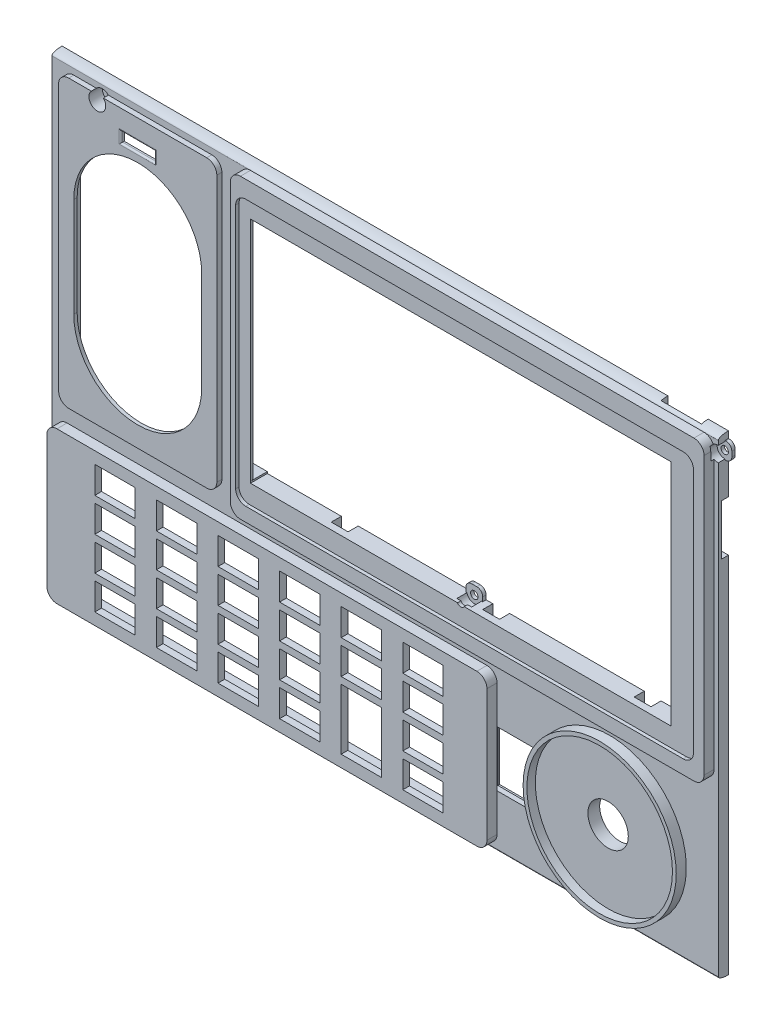
SolidWorks part; units mm, degrees
ref_plane "Front Plane" through (0, 0, 0) normal (0, 0, 1) x (1, 0, 0)
ref_plane "Top Plane" through (0, 0, 0) normal (0, 1, 0) x (1, 0, 0)
ref_plane "Right Plane" through (0, 0, 0) normal (1, 0, 0) x (0, 0, -1)
sketch "Sketch1" plane through (0, 0, 0) normal (0, 0, 1) x (1, 0, 0)
  line L1 (99, -70) -> (-99, -70)
  line L2 (99, -70) -> (99, 70)
  line L3 (99, 70) -> (-99, 70)
  line L4 (-99, -70) -> (-99, 70)
  line L5 (99, -70) -> (-99, 70) construction
  line L6 (99, 70) -> (-99, -70) construction
  point P0 (0, 0)
  dimension "D1" = 198
  dimension "D2" = 140
extrude "main_body" add sketch "Sketch1" along normal blind 3
fillet "long_corners" radius 3 2 edges at (0, 70, 3) (0, -70, 3) second distance 1 first distance on face at (0, 70, 1.5) first distance on face at (0, -70, 1.5)
sketch "Sketch2" plane through (0, 0, 3) normal (0, 0, 1) x (1, 0, 0)
  line L0 (-99, 24.75) -> (99, 24.75) construction
  line L1 (-99, 69) -> (-99, -69) construction
  line L2 (99, -69) -> (99, 69) construction
  line L3 (99, 69) -> (-99, 69) construction
  line L4 (-48.5, -17.75) -> (-95.5, -17.75)
  line L5 (-48.5, -17.75) -> (-48.5, 67.25)
  line L6 (-48.5, 67.25) -> (-95.5, 67.25)
  line L7 (-95.5, -17.75) -> (-95.5, 67.25)
  line L8 (-48.5, -17.75) -> (-95.5, 67.25) construction
  line L9 (-48.5, 67.25) -> (-95.5, -17.75) construction
  point P6 (-72, 24.75)
  dimension "D1" = 85
  dimension "D2" = 47
  dimension "D3" = 27
  dimension "D4" = 44.25
extrude "speaker" add sketch "Sketch2" along normal blind 1.5
fillet "speaker_corners" radius 3 4 edges at (-95.5, 67.25, 3.75) (-95.5, -17.75, 3.75) (-48.5, -17.75, 3.75) (-48.5, 67.25, 3.75)
sketch "Sketch19" plane through (0, 0, 4.5) normal (0, 0, 1) x (1, 0, 0)
  line L0 (-72, 67.25) -> (-72, -17.75) construction
  line L1 (-51.5, 67.25) -> (-92.5, 67.25) construction
  line L2 (-92.5, -17.75) -> (-51.5, -17.75) construction
  line L3 (-72, 7.25) -> (-72, 36.75) construction
  line L4 (-95.5, 64.25) -> (-95.5, -14.75) construction
  line L5 (-95.5, 24.75) -> (-48.5, 24.75) construction
  line L6 (-48.5, -14.75) -> (-48.5, 64.25) construction
  line L7 (-91, 7.25) -> (-91, 36.75)
  line L8 (-53, 7.25) -> (-53, 36.75)
  arc A0 (-91, 7.25) -> (-53, 7.25) centre (-72, 7.25) ccw
  arc A1 (-53, 36.75) -> (-91, 36.75) centre (-72, 36.75) ccw
  point P14 (-72, 22)
  point P19 (-72, -11.75)
  point P20 (-72, 55.75)
  dimension "D2" = 67.5
  dimension "D1" = 38
  dimension "D3" = 11.5
  dimension "D4" = 6
extrude "speaker_cut" cut sketch "Sketch19" against normal through all
sketch "Sketch21" plane through (0, 0, 0) normal (0, 0, -1) x (-1, 0, 0)
  line L0 (72, -11.75) -> (72, 55.75) construction
  line L2 (53, 7.25) -> (53, 36.75) construction
  line L3 (53, 22) -> (91, 22) construction
  line L4 (91, 36.75) -> (91, 7.25) construction
  line L5 (50.5, 61) -> (93.5, 61)
  line L6 (50.5, 61) -> (50.5, -17)
  line L7 (50.5, -17) -> (93.5, -17)
  line L8 (93.5, 61) -> (93.5, -17)
  line L9 (50.5, 61) -> (93.5, -17) construction
  line L10 (50.5, -17) -> (93.5, 61) construction
  arc A0 (53, 7.25) -> (91, 7.25) centre (72, 7.25) ccw construction
  arc A1 (91, 36.75) -> (53, 36.75) centre (72, 36.75) ccw construction
  point P14 (72, 22)
  dimension "D1" = 43
  dimension "D2" = 78
extrude "speaker_slot" cut sketch "Sketch21" against normal blind 3.5
sketch "Sketch3" plane through (0, 0, 3) normal (0, 0, 1) x (1, 0, 0)
  line L0 (-99, 24.875) -> (99, 24.875) construction
  line L1 (-99, 69) -> (-99, -69) construction
  line L2 (99, -69) -> (99, 69) construction
  line L4 (-48.5, -14.75) -> (-48.5, 64.25) construction
  line L5 (97.75, -19.25) -> (-43, -19.25)
  line L6 (97.75, -19.25) -> (97.75, 69)
  line L7 (97.75, 69) -> (-43, 69)
  line L8 (-43, -19.25) -> (-43, 69)
  line L9 (97.75, -19.25) -> (-43, 69) construction
  line L10 (97.75, 69) -> (-43, -19.25) construction
  line L11 (99, 70) -> (-99, 70) construction
  point P8 (27.375, 24.875)
  dimension "D1" = 1
  dimension "D2" = 88.25
  dimension "D3" = 140.75
  dimension "D4" = 1.25
  dimension "D5" = 5.5
extrude "lcd" add sketch "Sketch3" along normal blind 3
fillet "lcd_corners" radius 3 4 edges at (97.75, -19.25, 4.5) (-43, -19.25, 4.5)
sketch "Sketch9" plane through (0, 0, 6) normal (0, 0, 1) x (1, 0, 0)
  line L0 (-43, 24.375) -> (97.75, 24.375) construction
  line L1 (-43, 66) -> (-43, -16.25) construction
  line L2 (97.75, -16.25) -> (97.75, 66) construction
  line L3 (-40, -19.25) -> (94.75, -19.25) construction
  line L4 (94.6, -15.125) -> (-41.4, -15.125)
  line L5 (94.6, -15.125) -> (94.6, 63.875)
  line L6 (94.6, 63.875) -> (-41.4, 63.875)
  line L7 (-41.4, -15.125) -> (-41.4, 63.875)
  line L8 (94.6, -15.125) -> (-41.4, 63.875) construction
  line L9 (94.6, 63.875) -> (-41.4, -15.125) construction
  line L10 (94.75, 69) -> (-40, 69) construction
  line L11 (97.75, -16.25) -> (97.75, 66) construction
  point P6 (26.6, 24.375)
  dimension "D1" = 136
  dimension "D2" = 79
  dimension "D3" = 1.6
  dimension "D4" = 4.125
  dimension "D5" = 5.125
  dimension "D6" = 3.15
extrude "lcd_front" cut sketch "Sketch9" against normal blind 1
fillet "lcd_front_corners" radius 3 4 edges at (94.6, -15.125, 5.5) (94.6, 63.875, 5.5) (-41.4, 63.875, 5.5) (-41.4, -15.125, 5.5)
sketch "Sketch10" plane through (0, 0, 0) normal (0, 0, -1) x (-1, 0, 0)
  line L0 (-94.6, -12.125) -> (-94.6, 60.875) construction
  line L1 (-91.6, 63.875) -> (38.4, 63.875) construction
  line L2 (41.4, 63.875) -> (41.4, -15.125) construction
  line L3 (-94.6, 63.875) -> (41.4, 63.875) construction
  line L4 (38, -9.5) -> (-87, -9.5)
  line L5 (38, -9.5) -> (38, 58.5)
  line L6 (38, 58.5) -> (-87, 58.5)
  line L7 (-87, -9.5) -> (-87, 58.5)
  line L8 (-87, -9.5) -> (38, 58.5) construction
  line L9 (-87, 58.5) -> (38, -9.5) construction
  line L10 (-99, -70) -> (-99, 70) construction
  line L11 (-99, 70) -> (99, 70) construction
  line L13 (38.4, -15.125) -> (-91.6, -15.125) construction
  dimension "D1" = 125
  dimension "D2" = 68
  dimension "D3" = 12
  dimension "D4" = 3.4
  dimension "D5" = 11.5
  dimension "D6" = 5.375
  dimension "D7" = 7.6
  dimension "D8" = 5.375
  dimension "D9" = 5.625
extrude "lcd_back" cut sketch "Sketch10" against normal through all
sketch "Sketch56" plane through (0, 0, 0) normal (0, 0, -1) x (-1, 0, 0)
  line L0 (-87, -9.5) -> (38, -9.5) construction
  line L1 (-79, -9.5) -> (-74, -9.5)
  line L2 (-79, -9.5) -> (-79, -12.5)
  line L3 (-79, -12.5) -> (-74, -12.5)
  line L4 (-74, -9.5) -> (-74, -12.5)
  line L5 (38, 58.5) -> (-87, 58.5) construction
  line L6 (-34, -9.5) -> (-29, -9.5)
  line L7 (-34, -9.5) -> (-34, -12.5)
  line L8 (-34, -12.5) -> (-29, -12.5)
  line L9 (-29, -9.5) -> (-29, -12.5)
  line L10 (11, -9.5) -> (16, -9.5)
  line L11 (11, -9.5) -> (11, -12.5)
  line L12 (11, -12.5) -> (16, -12.5)
  line L13 (16, -9.5) -> (16, -12.5)
  line L14 (-79, 58.5) -> (-74, 58.5)
  line L15 (-79, 58.5) -> (-79, 61.5)
  line L16 (-79, 61.5) -> (-74, 61.5)
  line L17 (-74, 58.5) -> (-74, 61.5)
  line L18 (38, -9.5) -> (38, 58.5) construction
  line L19 (-34, 58.5) -> (-29, 58.5)
  line L20 (-34, 58.5) -> (-34, 61.5)
  line L21 (-34, 61.5) -> (-29, 61.5)
  line L22 (-29, 58.5) -> (-29, 61.5)
  line L23 (11, 58.5) -> (16, 58.5)
  line L24 (11, 58.5) -> (11, 61.5)
  line L25 (11, 61.5) -> (16, 61.5)
  line L26 (16, 58.5) -> (16, 61.5)
  line L27 (38, 58) -> (42, 58)
  line L28 (38, 58) -> (38, -9)
  line L29 (38, -9) -> (42, -9)
  line L30 (42, 58) -> (42, -9)
  line L31 (-99, -70) -> (-99, 70) construction
  line L32 (-99, 70) -> (99, 70) construction
  point P34 (-29, -11)
  dimension "D1" = 5
  dimension "D2" = 5
  dimension "D3" = 5
  dimension "D4" = 5
  dimension "D5" = 5
  dimension "D6" = 5
  dimension "D7" = 67
  dimension "D8" = 4
  dimension "D9" = 3
  dimension "D10" = 3
  dimension "D11" = 3
  dimension "D12" = 3
  dimension "D13" = 3
  dimension "D14" = 3
  dimension "D15" = 40
  dimension "D16" = 40
  dimension "D17" = 20
  dimension "D18" = 20
  dimension "D19" = 40
  dimension "D20" = 40
  dimension "D21" = 12
extrude "lcd_glue_points" cut sketch "Sketch56" against normal blind 3
sketch "Sketch4" plane through (0, 0, 3) normal (0, 0, 1) x (1, 0, 0)
  line L0 (-99, -45.75) -> (99, -45.75) construction
  line L1 (-99, 69) -> (-99, -69) construction
  line L2 (99, -69) -> (99, 69) construction
  line L4 (-92.5, -17.75) -> (-51.5, -17.75) construction
  line L5 (33.25, -68.25) -> (-97.5, -68.25)
  line L6 (33.25, -68.25) -> (33.25, -23.25)
  line L7 (33.25, -23.25) -> (-97.5, -23.25)
  line L8 (-97.5, -68.25) -> (-97.5, -23.25)
  line L9 (33.25, -68.25) -> (-97.5, -23.25) construction
  line L10 (33.25, -23.25) -> (-97.5, -68.25) construction
  line L11 (-99, -70) -> (99, -70) construction
  point P8 (-32.125, -45.75)
  dimension "D1" = 1.75
  dimension "D2" = 130.75
  dimension "D3" = 45
  dimension "D4" = 1.5
  dimension "D5" = 5.5
extrude "keypad" add sketch "Sketch4" along normal blind 3
fillet "keypad_corners" radius 3 4 edges at (-97.5, -68.25, 4.5) (33.25, -68.25, 4.5) (33.25, -23.25, 4.5) (-97.5, -23.25, 4.5)
sketch "Sketch25" plane through (0, 0, 6) normal (0, 0, 1) x (1, 0, 0)
  line L0 (-97.5, -30.75) -> (33.25, -30.75) construction
  line L1 (30.25, -23.25) -> (-94.5, -23.25) construction
  line L2 (-94.5, -68.25) -> (30.25, -68.25) construction
  line L3 (-77.25, -23.25) -> (-77.25, -68.25) construction
  line L5 (-34.65, -64.75) -> (33.25, -64.75) construction
  line L6 (-97.5, -26.25) -> (-97.5, -65.25) construction
  line L11 (33.25, -65.25) -> (33.25, -26.25) construction
  line L12 (-58.95, -23.25) -> (-58.95, -68.25) construction
  line L13 (-97.5, -40.75) -> (33.25, -40.75) construction
  line L14 (30.25, -23.25) -> (-94.5, -23.25) construction
  line L15 (-40.65, -23.25) -> (-40.65, -68.25) construction
  line L16 (-94.5, -68.25) -> (30.25, -68.25) construction
  line L17 (-71.25, -34.75) -> (-83.25, -34.75)
  line L18 (-22.35, -23.25) -> (-22.35, -68.25) construction
  line L19 (-97.5, -50.75) -> (33.25, -50.75) construction
  line L20 (-4.05, -23.25) -> (-4.05, -68.25) construction
  line L21 (-71.25, -34.75) -> (-71.25, -26.75)
  line L22 (14.25, -23.25) -> (14.25, -68.25) construction
  line L23 (-97.5, -26.25) -> (-97.5, -65.25) construction
  line L24 (-97.5, -60.75) -> (33.25, -60.75) construction
  line L25 (-71.25, -26.75) -> (-83.25, -26.75)
  line L26 (-83.25, -34.75) -> (-83.25, -26.75)
  line L27 (-71.25, -34.75) -> (-83.25, -26.75) construction
  line L28 (-71.25, -26.75) -> (-83.25, -34.75) construction
  line L29 (-71.25, -44.75) -> (-83.25, -44.75)
  line L30 (-71.25, -44.75) -> (-71.25, -36.75)
  line L31 (-71.25, -36.75) -> (-83.25, -36.75)
  line L32 (-83.25, -44.75) -> (-83.25, -36.75)
  line L33 (-71.25, -44.75) -> (-83.25, -36.75) construction
  line L34 (-71.25, -36.75) -> (-83.25, -44.75) construction
  line L35 (-71.25, -54.75) -> (-83.25, -54.75)
  line L36 (-71.25, -54.75) -> (-71.25, -46.75)
  line L37 (-71.25, -46.75) -> (-83.25, -46.75)
  line L38 (-83.25, -54.75) -> (-83.25, -46.75)
  line L39 (-71.25, -54.75) -> (-83.25, -46.75) construction
  line L40 (-71.25, -46.75) -> (-83.25, -54.75) construction
  line L41 (-71.25, -64.75) -> (-83.25, -64.75)
  line L42 (-71.25, -64.75) -> (-71.25, -56.75)
  line L43 (-71.25, -56.75) -> (-83.25, -56.75)
  line L44 (-83.25, -64.75) -> (-83.25, -56.75)
  line L45 (-71.25, -64.75) -> (-83.25, -56.75) construction
  line L46 (-71.25, -56.75) -> (-83.25, -64.75) construction
  line L47 (-52.95, -34.75) -> (-64.95, -34.75)
  line L48 (-52.95, -34.75) -> (-52.95, -26.75)
  line L49 (-52.95, -26.75) -> (-64.95, -26.75)
  line L50 (-64.95, -34.75) -> (-64.95, -26.75)
  line L51 (-52.95, -34.75) -> (-64.95, -26.75) construction
  line L52 (-52.95, -26.75) -> (-64.95, -34.75) construction
  line L53 (-52.95, -44.75) -> (-64.95, -44.75)
  line L54 (-52.95, -44.75) -> (-52.95, -36.75)
  line L55 (-52.95, -36.75) -> (-64.95, -36.75)
  line L56 (-64.95, -44.75) -> (-64.95, -36.75)
  line L57 (-52.95, -44.75) -> (-64.95, -36.75) construction
  line L58 (-52.95, -36.75) -> (-64.95, -44.75) construction
  line L59 (-52.95, -54.75) -> (-64.95, -54.75)
  line L60 (-52.95, -54.75) -> (-52.95, -46.75)
  line L61 (-52.95, -46.75) -> (-64.95, -46.75)
  line L62 (-64.95, -54.75) -> (-64.95, -46.75)
  line L63 (-52.95, -54.75) -> (-64.95, -46.75) construction
  line L64 (-52.95, -46.75) -> (-64.95, -54.75) construction
  line L65 (-52.95, -64.75) -> (-64.95, -64.75)
  line L66 (-52.95, -64.75) -> (-52.95, -56.75)
  line L67 (-52.95, -56.75) -> (-64.95, -56.75)
  line L68 (-64.95, -64.75) -> (-64.95, -56.75)
  line L69 (-52.95, -64.75) -> (-64.95, -56.75) construction
  line L70 (-52.95, -56.75) -> (-64.95, -64.75) construction
  line L71 (-34.65, -34.75) -> (-46.65, -34.75)
  line L72 (-34.65, -34.75) -> (-34.65, -26.75)
  line L73 (-34.65, -26.75) -> (-46.65, -26.75)
  line L74 (-46.65, -34.75) -> (-46.65, -26.75)
  line L75 (-34.65, -34.75) -> (-46.65, -26.75) construction
  line L76 (-34.65, -26.75) -> (-46.65, -34.75) construction
  line L77 (-34.65, -44.75) -> (-46.65, -44.75)
  line L78 (-34.65, -44.75) -> (-34.65, -36.75)
  line L79 (-34.65, -36.75) -> (-46.65, -36.75)
  line L80 (-46.65, -44.75) -> (-46.65, -36.75)
  line L81 (-34.65, -44.75) -> (-46.65, -36.75) construction
  line L82 (-34.65, -36.75) -> (-46.65, -44.75) construction
  line L83 (-34.65, -54.75) -> (-46.65, -54.75)
  line L84 (-34.65, -54.75) -> (-34.65, -46.75)
  line L85 (-34.65, -46.75) -> (-46.65, -46.75)
  line L86 (-46.65, -54.75) -> (-46.65, -46.75)
  line L87 (-34.65, -54.75) -> (-46.65, -46.75) construction
  line L88 (-34.65, -46.75) -> (-46.65, -54.75) construction
  line L89 (-34.65, -64.75) -> (-46.65, -64.75)
  line L90 (-34.65, -64.75) -> (-34.65, -56.75)
  line L91 (-34.65, -56.75) -> (-46.65, -56.75)
  line L92 (-46.65, -64.75) -> (-46.65, -56.75)
  line L93 (-34.65, -64.75) -> (-46.65, -56.75) construction
  line L94 (-34.65, -56.75) -> (-46.65, -64.75) construction
  line L95 (-16.35, -34.75) -> (-28.35, -34.75)
  line L96 (-16.35, -34.75) -> (-16.35, -26.75)
  line L97 (-16.35, -26.75) -> (-28.35, -26.75)
  line L98 (-28.35, -34.75) -> (-28.35, -26.75)
  line L99 (-16.35, -34.75) -> (-28.35, -26.75) construction
  line L100 (-16.35, -26.75) -> (-28.35, -34.75) construction
  line L101 (-16.35, -44.75) -> (-28.35, -44.75)
  line L102 (-16.35, -44.75) -> (-16.35, -36.75)
  line L103 (-16.35, -36.75) -> (-28.35, -36.75)
  line L104 (-28.35, -44.75) -> (-28.35, -36.75)
  line L105 (-16.35, -44.75) -> (-28.35, -36.75) construction
  line L106 (-16.35, -36.75) -> (-28.35, -44.75) construction
  line L111 (-16.35, -54.75) -> (-28.35, -54.75)
  line L112 (-16.35, -54.75) -> (-16.35, -46.75)
  line L113 (-16.35, -46.75) -> (-28.35, -46.75)
  line L114 (-28.35, -54.75) -> (-28.35, -46.75)
  line L115 (-16.35, -54.75) -> (-28.35, -46.75) construction
  line L116 (-16.35, -46.75) -> (-28.35, -54.75) construction
  line L117 (-16.35, -64.75) -> (-28.35, -64.75)
  line L118 (-16.35, -64.75) -> (-16.35, -56.75)
  line L119 (-16.35, -56.75) -> (-28.35, -56.75)
  line L120 (-28.35, -64.75) -> (-28.35, -56.75)
  line L121 (-16.35, -64.75) -> (-28.35, -56.75) construction
  line L122 (-16.35, -56.75) -> (-28.35, -64.75) construction
  line L127 (1.95, -34.75) -> (-10.05, -34.75)
  line L128 (1.95, -34.75) -> (1.95, -26.75)
  line L129 (1.95, -26.75) -> (-10.05, -26.75)
  line L130 (-10.05, -34.75) -> (-10.05, -26.75)
  line L131 (1.95, -34.75) -> (-10.05, -26.75) construction
  line L132 (1.95, -26.75) -> (-10.05, -34.75) construction
  line L133 (20.25, -34.75) -> (8.25, -34.75)
  line L134 (20.25, -34.75) -> (20.25, -26.75)
  line L135 (20.25, -26.75) -> (8.25, -26.75)
  line L136 (8.25, -34.75) -> (8.25, -26.75)
  line L137 (20.25, -34.75) -> (8.25, -26.75) construction
  line L138 (20.25, -26.75) -> (8.25, -34.75) construction
  line L139 (1.95, -44.75) -> (-10.05, -44.75)
  line L140 (1.95, -44.75) -> (1.95, -36.75)
  line L141 (1.95, -36.75) -> (-10.05, -36.75)
  line L142 (-10.05, -44.75) -> (-10.05, -36.75)
  line L143 (1.95, -44.75) -> (-10.05, -36.75) construction
  line L144 (1.95, -36.75) -> (-10.05, -44.75) construction
  line L145 (20.25, -44.75) -> (8.25, -44.75)
  line L146 (20.25, -44.75) -> (20.25, -36.75)
  line L147 (20.25, -36.75) -> (8.25, -36.75)
  line L148 (8.25, -44.75) -> (8.25, -36.75)
  line L149 (20.25, -44.75) -> (8.25, -36.75) construction
  line L150 (20.25, -36.75) -> (8.25, -44.75) construction
  line L151 (20.25, -54.75) -> (8.25, -54.75)
  line L152 (20.25, -54.75) -> (20.25, -46.75)
  line L153 (20.25, -46.75) -> (8.25, -46.75)
  line L154 (8.25, -54.75) -> (8.25, -46.75)
  line L155 (20.25, -54.75) -> (8.25, -46.75) construction
  line L156 (20.25, -46.75) -> (8.25, -54.75) construction
  line L157 (20.25, -64.75) -> (8.25, -64.75)
  line L158 (20.25, -64.75) -> (20.25, -56.75)
  line L159 (20.25, -56.75) -> (8.25, -56.75)
  line L160 (8.25, -64.75) -> (8.25, -56.75)
  line L161 (20.25, -64.75) -> (8.25, -56.75) construction
  line L162 (20.25, -56.75) -> (8.25, -64.75) construction
  line L163 (1.95, -64.75) -> (-10.05, -64.75)
  line L164 (1.95, -64.75) -> (1.95, -46.75)
  line L165 (1.95, -46.75) -> (-10.05, -46.75)
  line L166 (-10.05, -64.75) -> (-10.05, -46.75)
  line L167 (1.95, -64.75) -> (-10.05, -46.75) construction
  line L168 (1.95, -46.75) -> (-10.05, -64.75) construction
  point P34 (-77.25, -30.75)
  point P39 (-77.25, -40.75)
  point P44 (-77.25, -50.75)
  point P49 (-77.25, -60.75)
  point P54 (-58.95, -30.75)
  point P59 (-58.95, -40.75)
  point P64 (-58.95, -50.75)
  point P69 (-58.95, -60.75)
  point P74 (-40.65, -30.75)
  point P79 (-40.65, -40.75)
  point P84 (-40.65, -50.75)
  point P89 (-40.65, -60.75)
  point P94 (-22.35, -30.75)
  point P99 (-22.35, -40.75)
  point P104 (-22.35, -50.75)
  point P109 (-22.35, -60.75)
  point P114 (-4.05, -30.75)
  point P119 (14.25, -30.75)
  point P124 (-4.05, -40.75)
  point P129 (14.25, -40.75)
  point P134 (14.25, -50.75)
  point P139 (14.25, -60.75)
  point P144 (-4.05, -55.75)
  dimension "D1" = 19
  dimension "D2" = 18.3
  dimension "D3" = 18.3
  dimension "D4" = 18.3
  dimension "D5" = 18.3
  dimension "D6" = 18.3
  dimension "D7" = 20.25
  dimension "D8" = 7.5
  dimension "D9" = 10
  dimension "D10" = 10
  dimension "D11" = 10
  dimension "D12" = 7.5
  dimension "D13" = 12
  dimension "D14" = 12
  dimension "D15" = 12
  dimension "D16" = 12
  dimension "D17" = 12
  dimension "D18" = 12
  dimension "D19" = 12
  dimension "D20" = 12
  dimension "D21" = 12
  dimension "D22" = 12
  dimension "D23" = 12
  dimension "D24" = 12
  dimension "D25" = 12
  dimension "D26" = 12
  dimension "D27" = 12
  dimension "D28" = 12
  dimension "D29" = 12
  dimension "D30" = 12
  dimension "D31" = 12
  dimension "D32" = 12
  dimension "D33" = 12
  dimension "D34" = 12
  dimension "D35" = 12
  dimension "D36" = 8
  dimension "D37" = 8
  dimension "D38" = 8
  dimension "D39" = 8
  dimension "D40" = 8
  dimension "D41" = 8
  dimension "D42" = 18
  dimension "D43" = 8
  dimension "D44" = 8
  dimension "D45" = 8
  dimension "D46" = 8
  dimension "D47" = 8
  dimension "D48" = 8
  dimension "D49" = 8
  dimension "D50" = 8
  dimension "D51" = 8
  dimension "D52" = 8
  dimension "D53" = 8
  dimension "D54" = 8
  dimension "D55" = 8
  dimension "D56" = 8
  dimension "D57" = 8
  dimension "D58" = 8
  dimension "D59" = 5
extrude "keypad_cuts_0.8" cut sketch "Sketch25" against normal through all
sketch "Sketch5" plane through (0, 0, 3) normal (0, 0, 1) x (1, 0, 0)
  line L0 (33.25, -45.75) -> (99, -45.75) construction
  line L1 (33.25, -65.25) -> (33.25, -26.25) construction
  line L2 (99, -69) -> (99, 69) construction
  circle A0 centre (66.75, -45.75) radius 22.75
  dimension "D1" = 45.5
  dimension "D2" = 32.25
  dimension "D3" = 33.5
extrude "vfo" add sketch "Sketch5" along normal blind 3
sketch "Sketch7" plane through (0, 0, 6) normal (0, 0, 1) x (1, 0, 0)
  line L0 (44, -45.75) -> (89.5, -45.75) construction
  line L1 (66.75, -23) -> (66.75, -68.5) construction
  circle A0 centre (66.75, -45.75) radius 22.75 construction
  circle A1 centre (66.75, -45.75) radius 22.75 construction
  circle A2 centre (66.75, -45.75) radius 6
  dimension "D1" = 12
extrude "vfo_encoder_knob_cut" cut sketch "Sketch7" against normal through all
sketch "esp32" plane through (0, 0, 0) normal (0, 0, -1) x (-1, 0, 0)
  line L0 (99, -70) -> (-99, -70) construction
  line L1 (-50.5, -37.5) -> (-32, -37.5)
  line L2 (-50.5, -37.5) -> (-50.5, -54)
  line L3 (-50.5, -54) -> (-32, -54)
  line L4 (-32, -37.5) -> (-32, -54)
  line L5 (-99, -70) -> (-99, 70) construction
  dimension "D1" = 16
  dimension "D2" = 48.5
  dimension "D3" = 16.5
  dimension "D4" = 18.5
extrude "esp32_can_cut" cut sketch "esp32" against normal blind 3
sketch "Sketch47" plane through (0, 0, 0) normal (0, 0, -1) x (-1, 0, 0)
  line L0 (-50.5, -54) -> (-32, -54) construction
  line L1 (-31, -55) -> (-58, -55)
  line L2 (-31, -55) -> (-31, -36.5)
  line L3 (-31, -36.5) -> (-58, -36.5)
  line L4 (-58, -55) -> (-58, -36.5)
  line L5 (-31, -55) -> (-58, -36.5) construction
  line L6 (-31, -36.5) -> (-58, -55) construction
  line L7 (-50.5, -37.5) -> (-50.5, -54) construction
  point P0 (-44.5, -45.75)
  dimension "D1" = 27
  dimension "D2" = 18.5
  dimension "D3" = 1
  dimension "D4" = 7.5
extrude "esp32_ex_cut" cut sketch "Sketch47" against normal blind 1.5
sketch "Sketch49" plane through (0, 0, 0) normal (0, 0, -1) x (-1, 0, 0)
  line L0 (72, 59.75) -> (72, 67.25) construction
  line L3 (51.5, 67.25) -> (92.5, 67.25) construction
  line L4 (77, 58.25) -> (67, 58.25)
  line L5 (77, 58.25) -> (77, 61.25)
  line L6 (77, 61.25) -> (67, 61.25)
  line L7 (67, 58.25) -> (67, 61.25)
  line L8 (77, 58.25) -> (67, 61.25) construction
  line L9 (77, 61.25) -> (67, 58.25) construction
  point P6 (72, 59.75)
  dimension "D1" = 10
  dimension "D2" = 3
  dimension "D3" = 7.5
extrude "amb_sensor" cut sketch "Sketch49" against normal through all
fillet "amb_corners" radius 0.5 4 edges at (-67, 59.75, 4.5) (-72, 61.25, 4.5) (-77, 59.75, 4.5) (-72, 58.25, 4.5)
sketch "Sketch55" plane through (0, 0, 0) normal (0, 0, -1) x (-1, 0, 0)
  line L0 (-99, -70) -> (-99, 70) construction
  line L5 (-93, 70) -> (-81, 70)
  line L6 (-93, 70) -> (-93, 58.5)
  line L11 (-93, 58.5) -> (-81, 58.5)
  line L12 (-81, 70) -> (-81, 58.5)
  line L13 (94.5, 48) -> (99, 48)
  line L14 (94.5, 48) -> (94.5, 33)
  line L15 (94.5, 33) -> (99, 33)
  line L16 (99, 48) -> (99, 33)
  line L17 (94.5, 48) -> (99, 33) construction
  line L18 (94.5, 33) -> (99, 48) construction
  line L23 (99, 65.5) -> (-99, 65.5) construction
  line L24 (99, -8.5) -> (-99, -8.5) construction
  line L35 (-99, -68) -> (99, -68) construction
  line L36 (99, -70) -> (-99, -70) construction
  line L42 (-99, 53) -> (-93, 53)
  line L43 (-99, 53) -> (-99, 38)
  line L44 (-99, 70) -> (99, 70) construction
  line L45 (-99, 38) -> (-93, 38)
  line L46 (99, 70) -> (99, -70) construction
  line L47 (-93, 53) -> (-93, 38)
  circle A1 centre (49.5, 65.5) radius 3
  circle A2 centre (-24.5, 65.5) radius 3
  circle A4 centre (49.5, -8.5) radius 3
  circle A6 centre (-68, -68) radius 3
  circle A7 centre (-1, -68) radius 3
  circle A9 centre (-32, 65.5) radius 3
  point P10 (96.75, 40.5)
  dimension "D8" = 6
  dimension "D9" = 6
  dimension "D13" = 6
  dimension "D18" = 2
  dimension "D19" = 6
  dimension "D21" = 6
  dimension "D22" = 6
  dimension "D1" = 12
  dimension "D3" = 11.5
  dimension "D4" = 0
  dimension "D5" = 6
  dimension "D6" = 4.5
  dimension "D11" = 49.5
  dimension "D12" = 123.5
  dimension "D14" = 7.5
  dimension "D15" = 61.5
  dimension "D24" = 100
  dimension "D25" = 15
  dimension "D26" = 4.5
  dimension "D27" = 0
  dimension "D28" = 22
  dimension "D29" = 49.5
  dimension "D30" = 67
  dimension "D31" = 6
  dimension "D32" = 15
  dimension "D33" = 0
  dimension "D34" = 17
extrude "conn_cutouts" cut sketch "Sketch55" against normal blind 2
fillet "Fillet1" radius 2 1 edges at (-38, 24.5, 3)
fillet "Fillet2" radius 5 1 edges at (-42, 24.5, 0)
sketch "Sketch57" plane through (0, 0, 0) normal (0, 0, -1) x (-1, 0, 0)
  line L0 (99, 70) -> (99, 48) construction
  line L1 (-24, -24.5) -> (89, -24.5)
  line L2 (-24, -24.5) -> (-24, -66.5)
  line L3 (-24, -66.5) -> (89, -66.5)
  line L4 (89, -24.5) -> (89, -66.5)
  line L5 (99, -70) -> (1.2361, -70) construction
  dimension "D1" = 113
  dimension "D2" = 42
  dimension "D3" = 10
  dimension "D4" = 3.5
extrude "keyboard_back" cut sketch "Sketch57" against normal blind 4
sketch "Sketch58" plane through (0, -9.5, 0) normal (0, 1, 0) x (1, 0, 0)
  line L1 (27, -1) -> (22, -1)
  line L2 (27, -1) -> (27, 0)
  line L3 (27, 0) -> (22, 0)
  line L4 (22, -1) -> (22, 0)
  line L5 (27, -1) -> (22, 0) construction
  line L6 (27, 0) -> (22, -1) construction
  line L7 (29, -3) -> (29, 0) construction
  line L9 (29, 0) -> (-11, 0) construction
  point P0 (24.5, -0.5)
  dimension "D1" = 1
  dimension "D2" = 5
  dimension "D3" = 2
  dimension "D4" = 0
extrude "behind_lcd_screew_mount" add sketch "Sketch58" along normal blind 3
sketch "Sketch59" plane through (-99, 0, 0) normal (-1, 0, 0) x (0, 0, 1)
  line L0 (0, 70) -> (0, 48) construction
  line L1 (0, -66.5) -> (1, -66.5)
  line L2 (0, -66.5) -> (0, -69.5)
  line L3 (0, -69.5) -> (1, -69.5)
  line L4 (1, -66.5) -> (1, -69.5)
  dimension "D1" = 1
  dimension "D2" = 3
  dimension "D3" = 66.5
extrude "keyb_screw_mount" add sketch "Sketch59" along normal blind 1
sketch "Sketch60" plane through (99, 0, 0) normal (1, 0, 0) x (0, 0, -1)
  line L0 (0, -70) -> (0, 38) construction
  line L1 (0, 68) -> (-1, 68)
  line L2 (0, 68) -> (0, 63)
  line L3 (0, 63) -> (-1, 63)
  line L4 (-1, 68) -> (-1, 63)
  dimension "D1" = 63
  dimension "D2" = 5
  dimension "D3" = 1
extrude "right_corner_screw_mount" add sketch "Sketch60" along normal blind 2
sketch "Sketch61" plane through (0, 0, 0) normal (0, 0, -1) x (-1, 0, 0)
  line L0 (-99, 70) -> (-93, 70) construction
  line L1 (-99, 68) -> (-99, 70) construction
  line L2 (-99, -9) -> (99, -9) construction
  line L3 (99, 70) -> (99, 48) construction
  line L5 (-99, -70) -> (-99, 38) construction
  line L6 (99, 70) -> (99, 48) construction
  line L7 (-3.2361, -70) -> (-65.7639, -70) construction
  line L8 (99, -69.5) -> (99, -70) construction
  line L9 (99, -70) -> (1.2361, -70) construction
  line L10 (-81, 70) -> (99, 70) construction
  circle A0 centre (-98.9, 65.5) radius 1.1
  circle A1 centre (-24.5, -9) radius 1.1
  circle A2 centre (98, -68) radius 1.1
  circle A3 centre (84, 65.5) radius 1.1
  dimension "D1" = 2.2
  dimension "D6" = 2.2
  dimension "D9" = 2.2
  dimension "D10" = 2.2
  dimension "D2" = 4.5
  dimension "D3" = 0.1
  dimension "D4" = 61
  dimension "D5" = 123.5
  dimension "D7" = 1
  dimension "D8" = 2
  dimension "D11" = 15
  dimension "D12" = 4.5
extrude "ui_screws" cut sketch "Sketch61" against normal through all
sketch "Sketch62" plane through (0, 0, 6) normal (0, 0, 1) x (1, 0, 0)
  line L0 (97.8, 65.5) -> (100, 65.5) construction
  line L1 (-98, -66.9) -> (-98, -69.1) construction
  line L2 (98.9, 66.6) -> (98.9, 64.4) construction
  line L4 (-96.9, -68) -> (-99.1, -68) construction
  circle A0 centre (24.5, -9) radius 2.25
  arc A1 (99, 66.5954) -> (99, 64.4046) centre (98.9, 65.5) ccw construction
  arc A2 (99, 64.4046) -> (99, 66.5954) centre (98.9, 65.5) ccw construction
  circle A3 centre (98.9, 65.5) radius 2.25
  arc A4 (-97.5417, -69) -> (-99, -67.5417) centre (-98, -68) ccw construction
  arc A5 (-98.4583, -69) -> (-97.5417, -69) centre (-98, -68) ccw construction
  arc A6 (-99, -67.5417) -> (-99, -68.4583) centre (-98, -68) ccw construction
  circle A7 centre (-98, -68) radius 2.25
  dimension "D1" = 4.5
  dimension "D2" = 4.5
  dimension "D3" = 4.5
extrude "ui_screw_head" cut sketch "Sketch62" against normal blind 3 from offset 2 offset against normal yes
fillet "ui_screw_mount_corners" radius 1.75 6 edges at (-100, -66.5, 0.5) (-100, -69.5, 0.5) (101, 63, 0.5) (101, 68, 0.5) (22, -6.5, 0.5) (27, -6.5, 0.5)
sketch "Sketch63" plane through (0, 0, 6) normal (0, 0, 1) x (1, 0, 0)
  circle A0 centre (66.75, -45.75) radius 21.625
  dimension "D1" = 43.25
extrude "enc_knob_slot" cut sketch "Sketch63" against normal blind 2.5
sketch "Sketch64" plane through (0, 0, 4.5) normal (0, 0, 1) x (1, 0, 0)
  circle A0 centre (-84, 65.5) radius 2.5
  dimension "D1" = 5
extrude "on_speaker_ui_screw_head" cut sketch "Sketch64" against normal blind 4
fillet "Fillet3" radius 2 4 edges at (-89, -66.5, 2) (-89, -24.5, 2) (24, -66.5, 2) (24, -24.5, 2)
